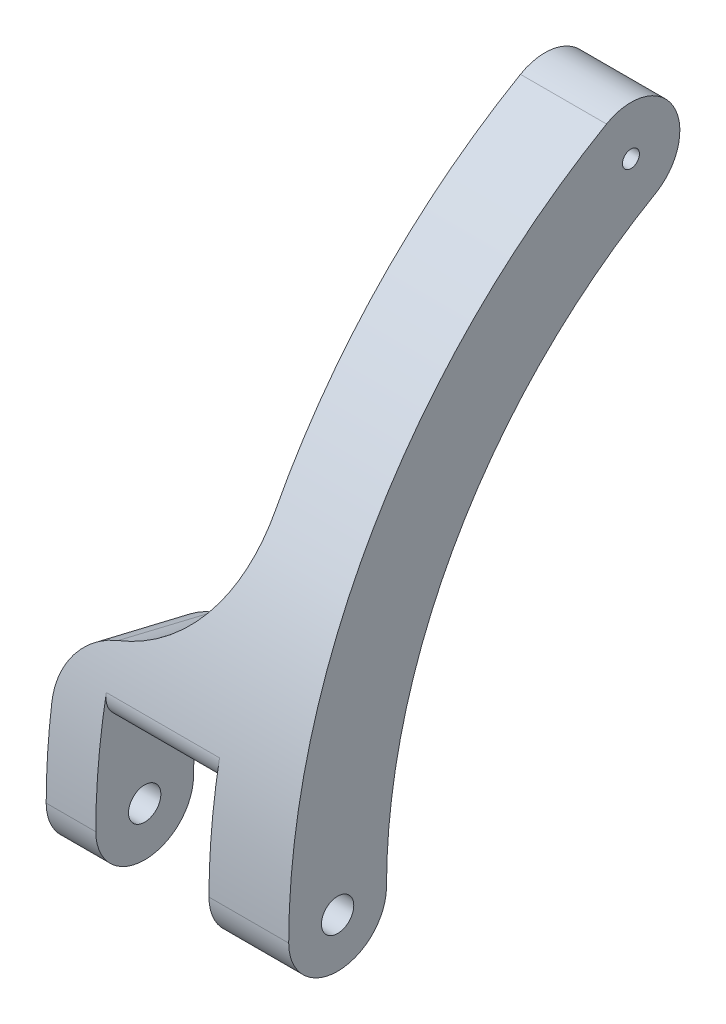
SolidWorks part; units mm, degrees
material "ABS"
ref_plane "Front Plane" through (0, 0, 0) normal (0, 0, 1) x (1, 0, 0)
ref_plane "Top Plane" through (0, 0, 0) normal (0, 1, 0) x (1, 0, 0)
ref_plane "Right Plane" through (0, 0, 0) normal (1, 0, 0) x (0, 0, -1)
sketch "Esquisse1" plane through (0, 0, 0) normal (1, 0, 0) x (0, 0, -1)
  arc A0 (-34.925, 0) -> (-17.4625, 30.2459) centre (0, 0) cw
  arc A1 (-41.275, 0) -> (-20.6375, 35.7452) centre (0, 0) cw
  arc A2 (-41.275, 0) -> (-34.925, 0) centre (-38.1, 0) ccw
  arc A3 (-17.4625, 30.2459) -> (-20.6375, 35.7452) centre (-19.05, 32.9956) ccw
  circle A4 centre (-38.1, 0) radius 1.05
  circle A5 centre (-19.05, 32.9956) radius 0.55
  dimension "D1" = 3.175
  dimension "D4" = 2.1
  dimension "D5" = 1.1
  dimension "D2" = 38.1
  dimension "D3" = 38.1
extrude "Boss.-Extru.1" add sketch "Esquisse1" along normal blind 5.588
sketch "Esquisse2" plane through (0, 0, 0) normal (-1, 0, 0) x (0, 0, 1)
  line L0 (40.1357, 9.6308) -> (33.961, 8.1492)
  arc A0 (34.925, 0) -> (17.4625, 30.2459) centre (0, 0) ccw construction
  arc A1 (34.925, 0) -> (41.275, 0) centre (38.1, 0) ccw construction
  arc A2 (41.275, 0) -> (20.6375, 35.7452) centre (0, 0) ccw construction
  arc A3 (34.925, 0) -> (33.961, 8.1492) centre (0, 0) ccw
  arc A4 (34.925, 0) -> (41.275, 0) centre (38.1, 0) ccw
  arc A5 (41.275, 0) -> (40.1357, 9.6308) centre (0, 0) ccw
  dimension "D1" = 8.89
extrude "Boss.-Extru.2" add sketch "Esquisse2" along normal blind 10.16
sketch "Esquisse3" plane through (0, 0, 0) normal (0, 1, 0) x (1, 0, 0)
  line L0 (-0.0898, -40.447) -> (-0.0898, -41.4442) construction
  line L1 (-6.9398, -43.2861) -> (0.4102, -43.2861)
  line L2 (-6.9398, -43.2861) -> (-6.9398, -30.9839)
  line L3 (-6.9398, -30.9839) -> (0.4102, -30.9839)
  line L4 (0.4102, -43.2861) -> (0.4102, -30.9839)
  line L5 (-6.4398, -40.447) -> (-6.4398, -41.4442) construction
  dimension "D1" = 0.5
  dimension "D2" = 0.5
extrude "Enlèv. mat.-Extru.1" cut sketch "Esquisse3" against normal mid plane 11.43
fillet "Congé1" radius 10.16 1 edges at (0, 8.89, 37.0483)
fillet "Congé2" radius 5.08 1 edges at (-10.16, 8.89, 37.0483)
sketch "Esquisse4" plane through (5.588, 0, 0) normal (1, 0, 0) x (0, 0, -1)
  circle A0 centre (-38.1, 0) radius 1.05
  circle A1 centre (-38.1, 0) radius 1.05 construction
extrude "Enlèv. mat.-Extru.2" cut sketch "Esquisse4" against normal through all and the other way through all
fillet "Congé3" radius 1.5 2 edges at (-3.2648, 5.715, 40.8774) (-3.2648, 5.715, 34.4542)
